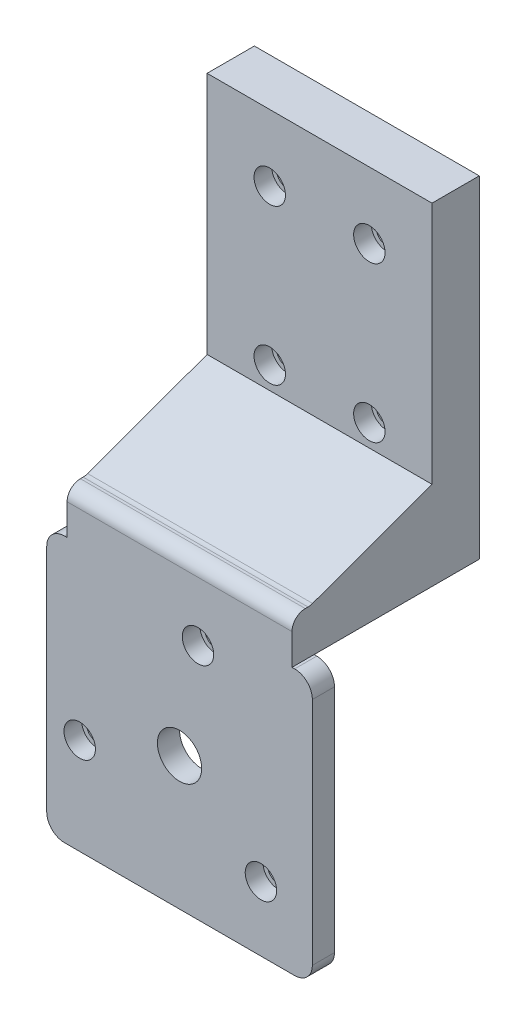
SolidWorks part; units mm, degrees
note: The reader was unsure of these and kept them because the rebuilt part matched: shared geometry of "Sketch1<3>", "Sketch1<4>", "Sketch1<5>".
ref_plane "Front Plane" through (0, 0, 0) normal (0, 0, 1) x (1, 0, 0)
ref_plane "Top Plane" through (0, 0, 0) normal (0, 1, 0) x (1, 0, 0)
ref_plane "Right Plane" through (0, 0, 0) normal (1, 0, 0) x (0, 0, -1)
sketch "Sketch1" plane through (0, 0, 0) normal (0, 0, 1) x (1, 0, 0)
  line L0 (-25.4, 60) -> (-25.4, 135)
  line L1 (-25.4, 135) -> (25.4, 135)
  line L2 (25.4, 135) -> (25.4, 60)
  line L4 (-11.25, 120) -> (11.25, 120) construction
  line L5 (-11.25, 120) -> (-11.25, 85) construction
  line L6 (-11.25, 85) -> (11.25, 85) construction
  line L7 (11.25, 120) -> (11.25, 85) construction
  line L9 (-25.4, 60) -> (25.4, 60)
  line L10 (-25.4, 70) -> (25.4, 70)
  line L16 (-26, 60) -> (26, 60)
  line L17 (-30, 56) -> (-30, 4)
  line L18 (-26, 0) -> (26, 0)
  line L19 (30, 56) -> (30, 4)
  circle A2 centre (-11.25, 120) radius 2.5
  circle A3 centre (11.25, 120) radius 2.5
  circle A4 centre (11.25, 85) radius 2.5
  circle A5 centre (-11.25, 85) radius 2.5
  arc A21 (26, 60) -> (30, 56) centre (26, 56) cw
  arc A22 (26, 0) -> (30, 4) centre (26, 4) ccw
  arc A23 (-30, 4) -> (-26, 0) centre (-26, 4) ccw
  arc A24 (-26, 60) -> (-30, 56) centre (-26, 56) ccw
  point P13 (0, 85)
  point P40 (0, 135)
  point P48 (-30, 0)
  point P51 (-30, 60)
  dimension "D4" = 5
  dimension "D10" = 4
  dimension "D2" = 50.8
  dimension "D5" = 35
  dimension "D7" = 22.5
  dimension "D6" = 15
  dimension "D11" = 25
  dimension "D12" = 10
  dimension "D9" = 60
extrude "5" add sketch "Sketch1" along normal blind 7.5 contours L0 L9 L2 L1 A5 A4 A3 A2
extrude "Boss-Extrude1" add sketch "Sketch1<3>" along normal blind 34.125 contours L10 L0 L9 L2
sketch "Sketch1<3>" plane through (0, 0, 0) normal (0, 0, 1) x (1, 0, 0) same geometry as "Sketch1"
extrude "Boss-Extrude2" add sketch "Sketch1<4>" along normal blind 5 from surface at 34.125
sketch "Sketch1<4>" plane through (0, 0, 0) normal (0, 0, 1) x (1, 0, 0) same geometry as "Sketch1"
chamfer "Chamfer1" distance 10 angle 70 1 edges at (0, 70, 7.5)
fillet "Fillet1" radius 3 2 edges at (0, 70, 39.125) (0, 70, 34.9748)
sketch "Sketch2" plane through (0, 0, 39.125) normal (0, 0, 1) x (1, 0, 0)
  line L0 (-30, 4) -> (-30, 56) construction
  circle A0 centre (0, 30) radius 5
  point P4 (-30, 30)
  dimension "D1" = 10
extrude "Cut-Extrude1" cut sketch "Sketch2" against normal through all
sketch "Sketch3" plane through (0, 0, 39.125) normal (0, 0, 1) x (1, 0, 0)
  line L0 (-22.5526, 21.7915) -> (0, 30) construction
  line L1 (0, 30) -> (0, 54) construction
  circle A0 centre (0, 30) radius 24 construction
  circle A1 centre (-22.5526, 21.7915) radius 2.5
  circle A2 centre (4.1676, 53.6354) radius 2.5
  circle A3 centre (18.3851, 14.5731) radius 2.5
  dimension "D1" = 48
  dimension "D2" = 5
  dimension "D3" = 110
  dimension "D4" = 3
extrude "Cut-Extrude2" cut sketch "Sketch3" against normal through all
sketch "Sketch4" plane through (0, 0, 39.125) normal (0, 0, 1) x (1, 0, 0)
  circle A0 centre (4.1676, 53.6354) radius 3.55
  circle A1 centre (-22.5526, 21.7915) radius 3.55
  circle A2 centre (18.3851, 14.5731) radius 3.55
  circle A3 centre (18.3851, 14.5731) radius 2.5 construction
  dimension "D1" = 7.1
extrude "Cut-Extrude3" cut sketch "Sketch4" against normal blind 4
sketch "Sketch5" plane through (0, 0, 7.5) normal (0, 0, 1) x (1, 0, 0)
  circle A0 centre (-11.25, 120) radius 3.55
  circle A1 centre (11.25, 120) radius 3.55
  circle A2 centre (-11.25, 85) radius 3.55
  circle A3 centre (11.25, 85) radius 3.55
  circle A4 centre (4.1676, 53.6354) radius 3.55 construction
extrude "Cut-Extrude4" cut sketch "Sketch5" against normal blind 4
extrude "Boss-Extrude3" add sketch "Sketch1<5>" against normal blind 3.18 contours L10 L0 L9 L2 | L0 L10 L2 L1 A5 A4 A3 A2
sketch "Sketch1<5>" plane through (0, 0, 0) normal (0, 0, 1) x (1, 0, 0) same geometry as "Sketch1"
equation "\"tube_length\"= 1.5ft"
equation "\"tube_width\"= 1in"
equation "\"tube_height\"= 2in"
equation "\"tube_thickness\"= 0.125in"
equation "\"D3@Sketch1\"=\"tube_thickness\""
equation "\"D1@Boss-Extrude1\"=\"tube_length\""
equation "\"D1@Sketch1\"=\"tube_width\""
equation "\"D2@Sketch1\"=\"tube_height\""
